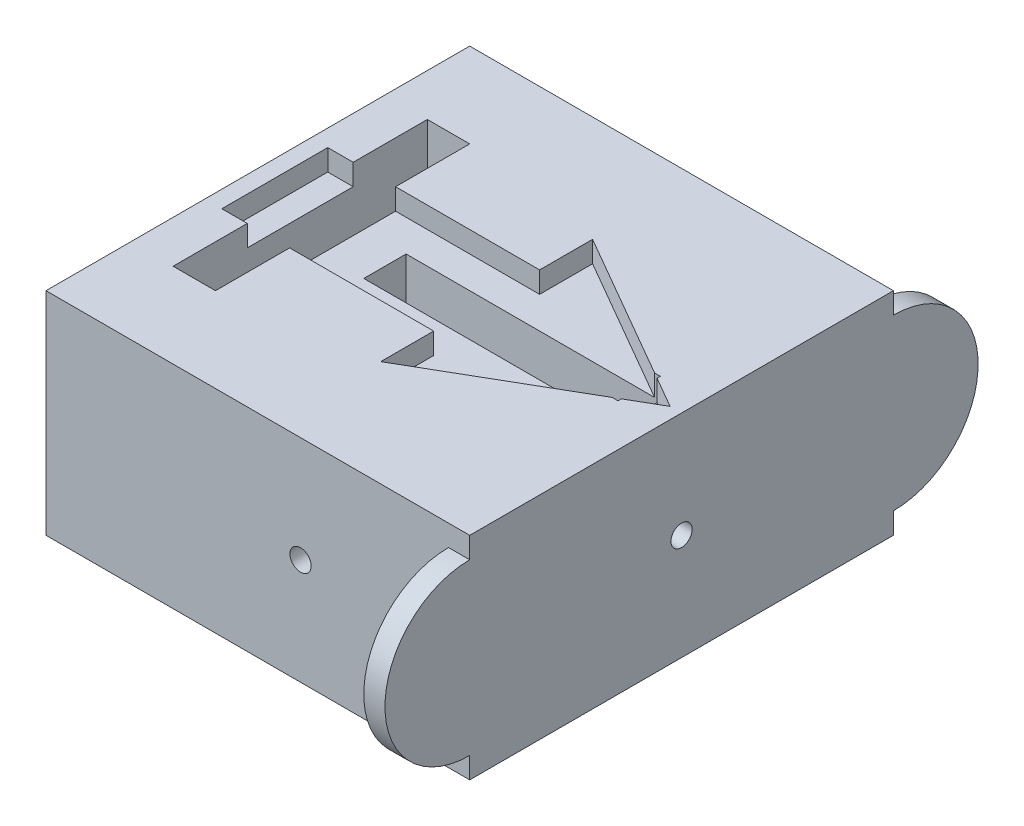
SolidWorks part; units mm, degrees
ref_plane "Front Plane" through (0, 0, 0) normal (0, 0, 1) x (1, 0, 0)
ref_plane "Top Plane" through (0, 0, 0) normal (0, 1, 0) x (1, 0, 0)
ref_plane "Right Plane" through (0, 0, 0) normal (1, 0, 0) x (0, 0, -1)
sketch "Sketch1" plane through (0, 0, 0) normal (0, 1, 0) x (1, 0, 0)
  line L1 (100, -100) -> (-100, -100)
  line L2 (100, -100) -> (100, 100)
  line L3 (100, 100) -> (-100, 100)
  line L4 (-100, -100) -> (-100, 100)
  line L5 (100, -100) -> (-100, 100) construction
  line L6 (100, 100) -> (-100, -100) construction
  point P0 (0, 0)
  dimension "D1" = 200
  dimension "D2" = 200
extrude "Boss-Extrude2" add sketch "Sketch1" along normal blind 100
sketch "Sketch2" plane through (100, 0, 0) normal (-1, 0, 0) x (0, 0, 1)
  line L0 (100, 100) -> (100, 0) construction
  line L1 (-100, 100) -> (-100, 0) construction
  circle A0 centre (100, 50) radius 40
  circle A1 centre (-100, 50) radius 40
  dimension "D1" = 80
extrude "Boss-Extrude3" add sketch "Sketch2" along normal blind 10
sketch "Sketch3" plane through (0, 100, 0) normal (0, 1, 0) x (1, 0, 0)
  line L0 (8, 25) -> (8, 50)
  line L1 (8, -25) -> (-92, -25) construction
  line L2 (8, -25) -> (8, 25) construction
  line L3 (8, 25) -> (-92, 25) construction
  line L4 (-92, -25) -> (-92, 25) construction
  line L5 (8, -25) -> (-92, 25) construction
  line L6 (8, 25) -> (-92, -25) construction
  line L7 (8, 50) -> (94.6025, 0)
  line L8 (94.6025, 0) -> (8, -50)
  line L9 (8, -50) -> (8, -25)
  line L10 (8, -25) -> (-92, -25)
  line L11 (-92, -25) -> (-92, 25)
  line L12 (-92, 25) -> (8, 25)
  line L13 (-100, 100) -> (-100, -100) construction
  point P0 (-42, 0)
  dimension "D1" = 50
  dimension "D2" = 100
  dimension "D3" = 100
  dimension "D4" = 60
  dimension "D5" = 8
extrude "Cut-Extrude1" cut sketch "Sketch3" against normal blind 10
sketch "Sketch4" plane through (0, 100, 0) normal (0, 1, 0) x (1, 0, 0)
  line L0 (-100, 100) -> (-100, -100) construction
  line L1 (80, -10) -> (-40, -10)
  line L2 (80, -10) -> (80, 10)
  line L3 (80, 10) -> (-40, 10)
  line L4 (-40, -10) -> (-40, 10)
  line L5 (80, -10) -> (-40, 10) construction
  line L6 (80, 10) -> (-40, -10) construction
  line L7 (100, -100) -> (100, 100) construction
  line L8 (-80, -60) -> (-60, -60)
  line L9 (-80, -60) -> (-80, 60)
  line L10 (-80, 60) -> (-60, 60)
  line L11 (-60, -60) -> (-60, 60)
  line L12 (-80, -60) -> (-60, 60) construction
  line L13 (-80, 60) -> (-60, -60) construction
  point P0 (20, 0)
  point P6 (-70, 0)
  dimension "D1" = 120
  dimension "D2" = 20
  dimension "D3" = 120
  dimension "D4" = 20
  dimension "D5" = 20
  dimension "D6" = 20
extrude "Cut-Extrude2" cut sketch "Sketch4" against normal through all
ref_point "Point2"
sketch "Sketch5" plane through (0, 0, 100) normal (0, 0, 1) x (1, 0, 0)
  line L0 (-100, 100) -> (-100, 0) construction
  circle A0 centre (20.1472, 50) radius 5
  point P2 (-100, 50)
  dimension "D1" = 10
extrude "Cut-Extrude3" cut sketch "Sketch5" against normal through all
sketch "Sketch6" plane through (-100, 0, 0) normal (-1, 0, 0) x (0, 0, 1)
  line L1 (-100, 100) -> (-100, 0) construction
  circle A0 centre (0, 50) radius 5
  point P5 (-100, 50)
  dimension "D1" = 10
extrude "Cut-Extrude4" cut sketch "Sketch6" against normal through all
ref_plane "Plane1" through (-70, 0, 0) normal (-1, 0, 0) x (0, 0, 1)
